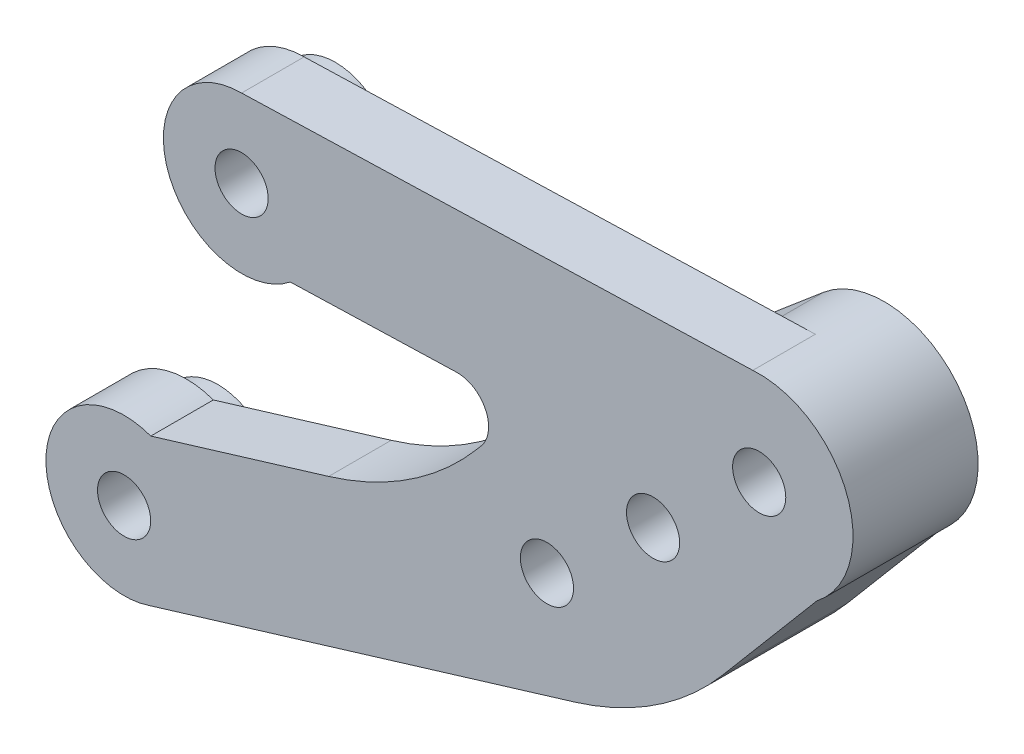
SolidWorks part; units mm, degrees
ref_plane "Front Plane" through (0, 0, 0) normal (0, 0, 1) x (1, 0, 0)
ref_plane "Top Plane" through (0, 0, 0) normal (0, 1, 0) x (1, 0, 0)
ref_plane "Right Plane" through (0, 0, 0) normal (1, 0, 0) x (0, 0, -1)
sketch "Sketch2" plane through (0, 0, 0) normal (0, 0, 1) x (1, 0, 0)
  line L0 (0, 0) -> (0, 21.6008) construction
  line L1 (40.6129, 21.6008) -> (0, 21.6008) construction
  line L2 (0, 0) -> (0, 21.6008) construction
  line L3 (0, 21.6008) -> (7.5129, 21.6008) construction
  line L4 (1.5758, -4.7452) -> (34.4569, 5.2326)
  line L5 (34.4569, 5.2326) -> (44.2966, 16.8647)
  line L6 (7.5129, 26.6008) -> (40.2038, 27.5868)
  line L10 (25.7338, 18.1463) -> (18.7287, 9.8651)
  line L11 (18.7287, 9.8651) -> (1.7066, 4.6997)
  line L12 (10.6292, 17.6907) -> (25.7338, 18.1463)
  circle A0 centre (0, 0) radius 1.7
  circle A1 centre (40.6129, 21.6008) radius 1.7
  circle A2 centre (7.5129, 21.6008) radius 1.7
  arc A3 (1.7066, 4.6997) -> (1.5758, -4.7452) centre (0, 0) ccw
  arc A4 (44.2966, 16.8647) -> (40.2038, 27.5868) centre (40.6129, 21.6008) ccw
  arc A5 (7.5129, 26.6008) -> (10.6292, 17.6907) centre (7.5129, 21.6008) ccw
  dimension "D1" = 3.4
  dimension "D2" = 3.4
  dimension "D3" = 3.4
  dimension "D8" = 10
  dimension "D9" = 12
  dimension "D10" = 10
  dimension "D4" = 46
  dimension "D5" = 33.1
  dimension "D7" = 22.87
  dimension "D11" = 9
  dimension "D12" = 9
  dimension "D13" = 15
extrude "Boss-Extrude1" add sketch "Sketch2" along normal blind 2 and the other way blind 2 contours L6 A5 A3 L4 L5 A4 A0 A1 A2 region at (22.1673, 13.7132, 0)
fillet "Fillet1" radius 20 2 edges at (34.4569, 5.2326, 0) (18.7287, 9.8651, 0)
sketch "Sketch3" plane through (0, 0, 2) normal (0, 0, 1) x (1, 0, 0)
  line L0 (44.2966, 16.8647) -> (30.687, 0.776)
  line L1 (38.2697, 9.7399) -> (44.2966, 16.8647) construction
  line L2 (30.687, 0.776) -> (37.0794, -4.6314)
  line L3 (37.0794, -4.6314) -> (43.0769, 2.4586)
  line L4 (44.2966, 16.8647) -> (50.689, 11.4573)
  line L5 (50.689, 11.4573) -> (44.6915, 4.3673)
  line L6 (43.0769, 2.4586) -> (32.5644, 0.4977)
  line L7 (32.5644, 0.4977) -> (44.8824, 15.0595)
  line L8 (44.8824, 15.0595) -> (44.6915, 4.3673)
  line L9 (32.5644, 0.4977) -> (31.9186, -0.2658) construction
  line L10 (44.8824, 15.0595) -> (45.5282, 15.8229) construction
  dimension "D1" = 1
  dimension "D2" = 2.5
extrude "Boss-Extrude2" [suppressed] add sketch "Sketch3" against normal up to surface (10 mm away)
fillet "Fillet2" [suppressed] radius 1
sketch "Sketch4" plane through (0, 0, 2) normal (0, 0, 1) x (1, 0, 0)
  line L7 (38.2697, 9.7399) -> (44.2966, 16.8647) construction
  line L8 (0, 0) -> (50000, 0) construction
  line L17 (44.2966, 16.8647) -> (44.8756, 15.9348)
  line L18 (40.6475, 27.6007) -> (47.8271, 27.6007)
  line L19 (47.8271, 27.6007) -> (51.8229, 19.889)
  line L20 (51.0994, 17.0478) -> (51.7638, 16.0989)
  line L21 (48.2447, 15.0489) -> (48.9091, 14.1)
  line L22 (48.3535, 17.9314) -> (-28630.4683, 40975.5336) construction
  arc A0 (40.6475, 27.6007) -> (44.2966, 16.8647) centre (40.6129, 21.6008) cw
  arc A1 (44.2966, 16.8647) -> (40.2038, 27.5868) centre (40.6129, 21.6008) ccw construction
  arc A3 (48.2447, 15.0489) -> (51.0994, 17.0478) centre (48.2713, 18.0488) ccw
  arc A4 (44.8756, 15.9348) -> (51.7638, 16.0989) centre (48.2713, 18.0488) ccw
  arc A5 (48.9091, 14.1) -> (51.8229, 19.889) centre (48.2713, 18.0488) ccw
  dimension "D1" = 6
  dimension "D2" = 8
  dimension "D3" = 55
extrude "Boss-Extrude3" [suppressed] add sketch "Sketch4" against normal up to surface (4 mm away)
fillet "Fillet3" [suppressed] radius 6
sketch "Sketch7" plane through (0, 0, -2) normal (0, 0, -1) x (-1, 0, 0)
  line L0 (-38.2697, 9.7399) -> (-44.2966, 16.8647) construction
  line L1 (-1.5758, -4.7452) -> (-28.8077, 3.5184) construction
  line L2 (-36.7334, 26.1779) -> (-21.684, 13.4222)
  line L4 (-44.2966, 16.8647) -> (-38.2697, 9.7399)
  line L6 (-40.6129, 21.6008) -> (-26.9361, 9.686) construction
  arc A2 (-38.2697, 9.7399) -> (-28.8077, 3.5184) centre (-23.0001, 22.6566) ccw
  arc A3 (-36.7334, 26.1779) -> (-44.2966, 16.8647) centre (-40.6129, 21.6008) ccw
  arc A4 (-28.8077, 3.5184) -> (-21.684, 13.4222) centre (-26.9361, 9.686) ccw
  arc A5 (-22.5414, 14.3724) -> (-13.0794, 8.1508) centre (-7.2719, 27.2891) ccw construction
  circle A6 centre (-40.6129, 21.6008) radius 1.7
  arc A7 (-40.2038, 27.5868) -> (-44.2966, 16.8647) centre (-40.6129, 21.6008) ccw construction
  point P5 (-33.0604, 15.194)
  point P10 (0, 0)
  point P21 (-28.8077, 3.5184)
extrude "Boss-Extrude4" add sketch "Sketch7" along normal blind 4
sketch "Sketch8" plane through (0, 0, -2) normal (0, 0, -1) x (-1, 0, 0)
  circle A0 centre (-7.5129, 21.6008) radius 1.7
  circle A1 centre (-7.5129, 21.6008) radius 3.7
  circle A2 centre (0, 0) radius 1.7
  circle A3 centre (0, 0) radius 3.7
  dimension "D1" = 2
  dimension "D2" = 2
  dimension "D3" = 3.4
  dimension "D4" = 3.4
extrude "Boss-Extrude5" add sketch "Sketch8" along normal blind 2
fillet "Fillet4" radius 2 1 edges at (25.7338, 18.1463, 0)
sketch "Sketch9" plane through (0, 0, -6) normal (0, 0, -1) x (-1, 0, 0)
  line L0 (-40.6129, 21.6008) -> (-26.9361, 9.686) construction
  circle A0 centre (-33.8268, 15.689) radius 1.7
  arc A2 (-28.8077, 3.5184) -> (-21.684, 13.4222) centre (-26.9361, 9.686) ccw construction
  circle A3 centre (-27.0407, 9.7772) radius 1.7
  point P8 (-26.9361, 9.686)
  dimension "D1" = 3.4
  dimension "D2" = 3.4
  dimension "D3" = 9
  dimension "D4" = 9
extrude "Cut-Extrude1" cut sketch "Sketch9" against normal through all
